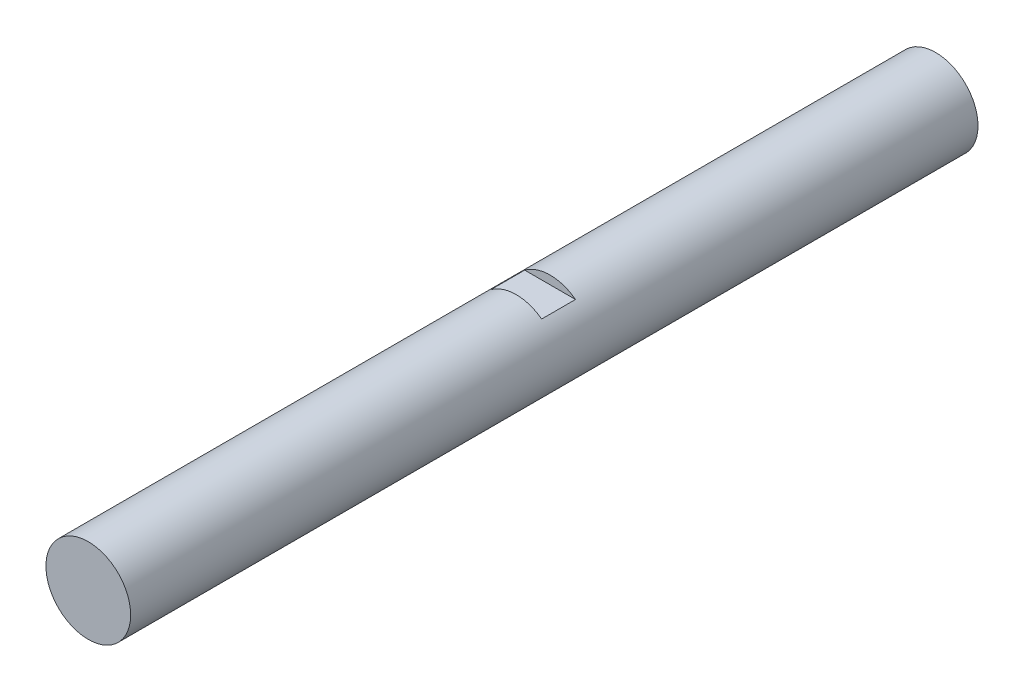
SolidWorks part; units mm, degrees
material "Хромистая нержавеющая сталь"
ref_plane "Спереди" through (0, 0, 0) normal (0, 0, 1) x (1, 0, 0)
ref_plane "Сверху" through (0, 0, 0) normal (0, 1, 0) x (1, 0, 0)
ref_plane "Справа" through (0, 0, 0) normal (1, 0, 0) x (0, 0, -1)
sketch "Эскиз1" plane through (0, 0, 0) normal (0, 0, 1) x (1, 0, 0)
  circle A0 centre (0, 0) radius 5
  dimension "D1" = 10
extrude "Бобышка-Вытянуть1" add sketch "Эскиз1" along normal blind 100
sketch "Эскиз2" plane through (0, 0, 0) normal (0, 0, -1) x (-1, 0, 0)
  line L0 (-3, 4) -> (3, 4)
  circle A0 centre (0, 0) radius 5 construction
  arc A1 (3, 4) -> (-3, 4) centre (0, 0) ccw
  dimension "D2" = 1
  dimension "D1" = 4
extrude "Вырез-Вытянуть1" cut sketch "Эскиз2" against normal blind 4 from offset 45.5 offset against normal yes
